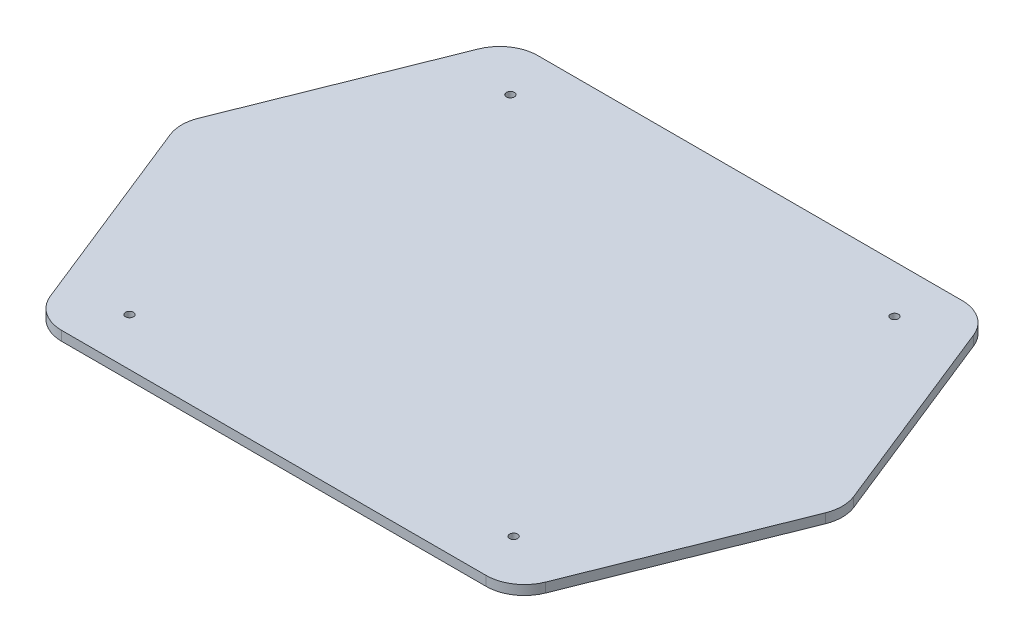
SolidWorks part; units mm, degrees
material "Acrílico (Impacto medio-alto)"
ref_plane "Alzado" through (0, 0, 0) normal (0, 0, 1) x (1, 0, 0)
ref_plane "Planta" through (0, 0, 0) normal (0, 1, 0) x (1, 0, 0)
ref_plane "Vista lateral" through (0, 0, 0) normal (1, 0, 0) x (0, 0, -1)
sketch "Sketch1" plane through (0, 0, 0) normal (0, 1, 0) x (1, 0, 0)
  line L0 (175, 0) -> (-175, 0) construction
  line L1 (-125, -125) -> (125, -125)
  line L3 (-125, 125) -> (125, 125)
  line L5 (-125, -125) -> (125, 125) construction
  line L6 (-125, 125) -> (125, -125) construction
  line L7 (-125, 125) -> (-175, 0)
  line L8 (-175, 0) -> (-125, -125)
  line L9 (125, 125) -> (175, 0)
  line L10 (175, 0) -> (125, -125)
  point P0 (0, 0)
  point P8 (0, 0)
  dimension "D1" = 250
  dimension "D2" = 250
  dimension "D3" = 350
extrude "Boss-Extrude1" add sketch "Sketch1" along normal blind 5
fillet "Fillet1" radius 20 6 edges at (-125, 2.5, 125) (125, 2.5, 125) (175, 2.5, 0) (125, 2.5, -125) (-125, 2.5, -125) (-175, 2.5, 0)
sketch "Sketch2" plane through (0, 5, 0) normal (0, 1, 0) x (1, 0, 0)
  line L0 (-100.8579, 100) -> (-100.8579, 125) construction
  line L1 (-100.8579, 100) -> (-135, 100) construction
  line L2 (0, -1000) -> (0, 49000) construction
  line L3 (-1000, 0) -> (49000, 0) construction
  line L4 (111.4593, 125) -> (-111.4593, 125) construction
  line L5 (-130.0289, 112.4278) -> (-172.0289, 7.4278) construction
  circle A0 centre (-100.8579, 100) radius 2.1
  circle A1 centre (100.8579, 100) radius 2.1
  circle A2 centre (-100.8579, -100) radius 2.1
  circle A3 centre (100.8579, -100) radius 2.1
  point P17 (0, 0)
  point P20 (-135, 100)
  dimension "D1" = 4.2
  dimension "D2" = 25
extrude "RF-Hole" cut sketch "Sketch2" against normal through all
